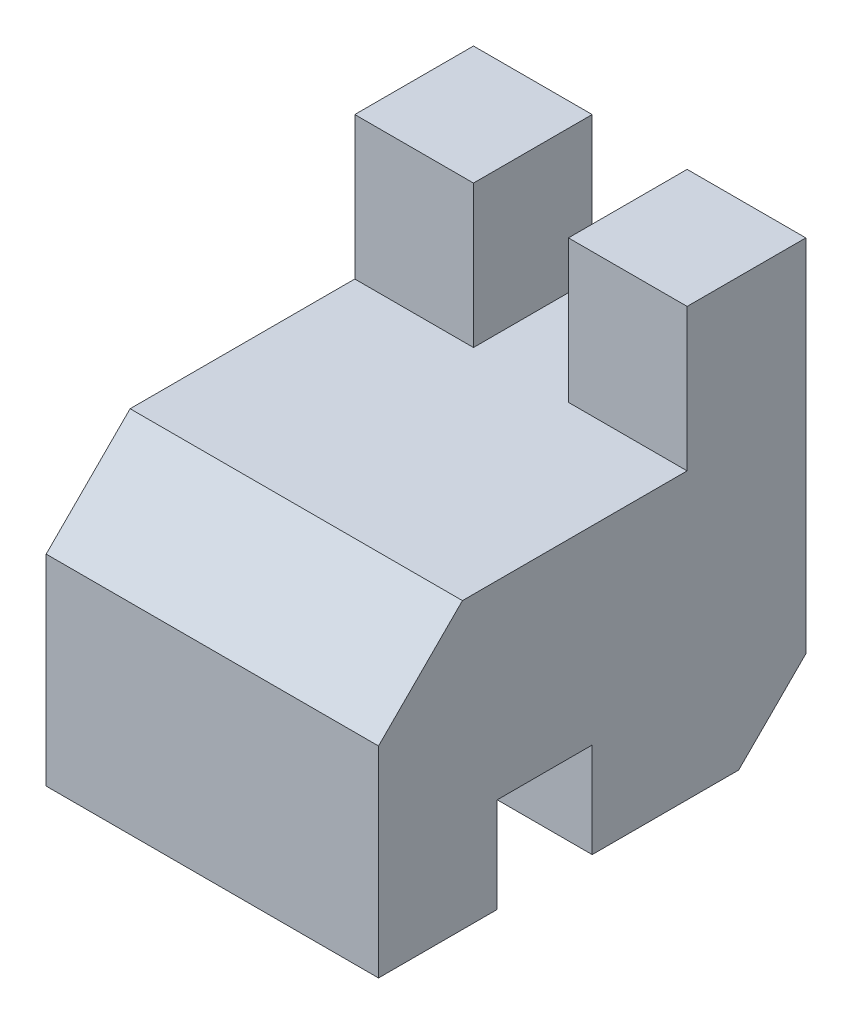
SolidWorks part; units mm, degrees
ref_plane "Front Plane" through (0, 0, 0) normal (0, 0, 1) x (1, 0, 0)
ref_plane "Top Plane" through (0, 0, 0) normal (0, 1, 0) x (1, 0, 0)
ref_plane "Right Plane" through (0, 0, 0) normal (1, 0, 0) x (0, 0, -1)
sketch "Sketch1" plane through (0, 0, 0) normal (1, 0, 0) x (0, 0, -1)
  line L0 (0, 0) -> (-30.8579, 0)
  line L1 (-30.8579, 0) -> (-30.8579, 20)
  line L2 (-30.8579, 20) -> (-50.8579, 20)
  line L3 (-50.8579, 20) -> (-50.8579, 0)
  line L4 (-50.8579, 0) -> (-75.8579, 0)
  line L5 (-75.8579, 0) -> (-75.8579, 42.3223)
  line L6 (-75.8579, 42.3223) -> (-58.1802, 60)
  line L7 (-58.1802, 60) -> (-10.8579, 60)
  line L8 (-10.8579, 60) -> (-10.8579, 90)
  line L9 (-10.8579, 90) -> (14.1421, 90)
  line L10 (14.1421, 90) -> (14.1421, 14.1421)
  line L11 (14.1421, 14.1421) -> (0, 0)
  dimension "D1" = 90
  dimension "D2" = 20
  dimension "D3" = 25
  dimension "D4" = 20
  dimension "D5" = 65
  dimension "D6" = 20
  dimension "D7" = 25
  dimension "D8" = 60
  dimension "D9" = 90
  dimension "D10" = 45
  dimension "D11" = 45
extrude "Boss-Extrude1" add sketch "Sketch1" along normal blind 35 and the other way blind 35
sketch "Sketch2" plane through (0, 0, 0) normal (0, 0, 1) x (1, 0, 0)
  line L0 (0, 90) -> (0, 60) construction
  line L1 (-35, 90) -> (35, 90) construction
  line L2 (-35, 60) -> (35, 60) construction
  line L3 (10, 60) -> (-10, 60)
  line L4 (-10, 60) -> (-10, 90)
  line L5 (-10, 90) -> (10, 90)
  line L6 (10, 90) -> (10, 60)
  point P9 (0, 60)
  dimension "D1" = 20
extrude "Cut-Extrude1" cut sketch "Sketch2" against normal blind 17 and the other way blind 13
